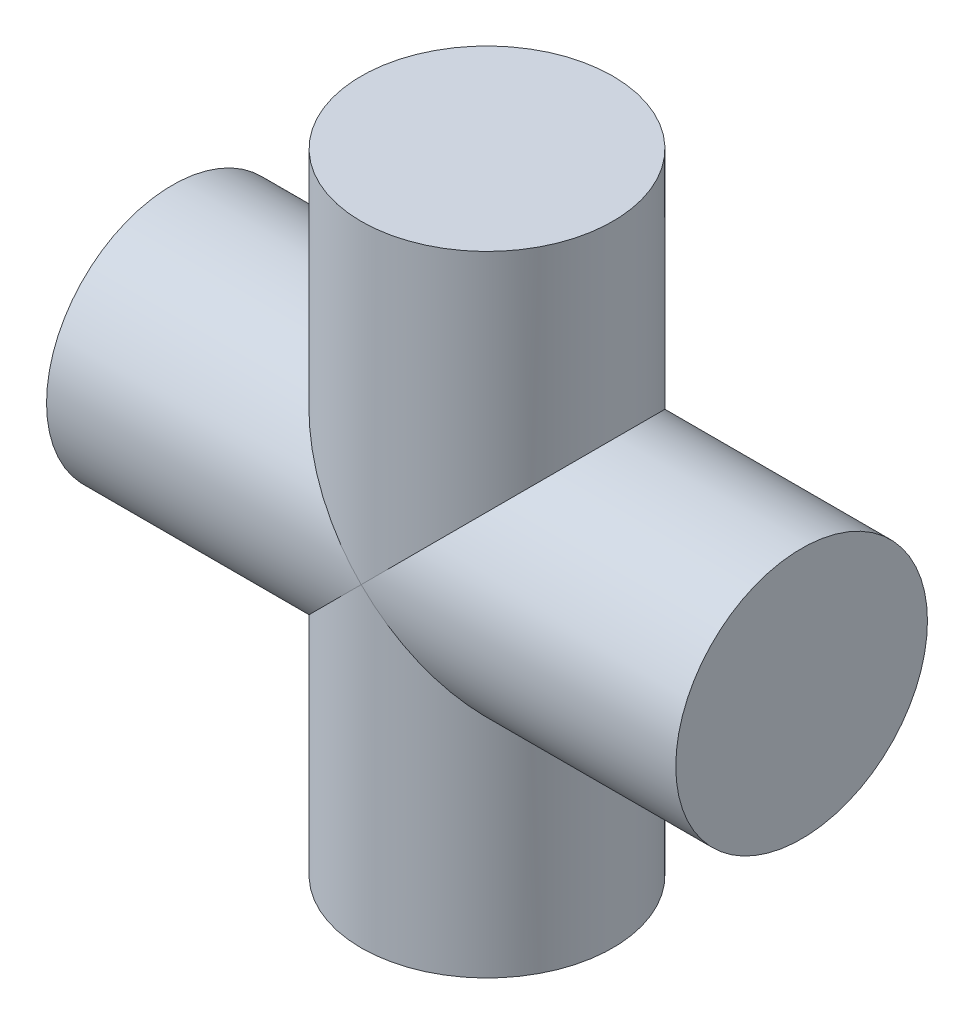
SolidWorks part; units mm, degrees
material "201 Annealed Stainless Steel (SS)"
ref_plane "Front Plane" through (0, 0, 0) normal (0, 0, 1) x (1, 0, 0)
ref_plane "Top Plane" through (0, 0, 0) normal (0, 1, 0) x (1, 0, 0)
ref_plane "Right Plane" through (0, 0, 0) normal (1, 0, 0) x (0, 0, -1)
sketch "Sketch1" plane through (0, 0, 0) normal (0, 1, 0) x (1, 0, 0)
  circle A0 centre (0, 0) radius 8
  dimension "D1" = 16
extrude "Boss-Extrude1" add sketch "Sketch1" along normal blind 20 and the other way blind 20
sketch "Sketch3" plane through (0, 0, 0) normal (1, 0, 0) x (0, 0, -1)
  circle A0 centre (0, 0) radius 8
  dimension "D1" = 16
extrude "Boss-Extrude2" add sketch "Sketch3" along normal blind 20 and the other way blind 20
